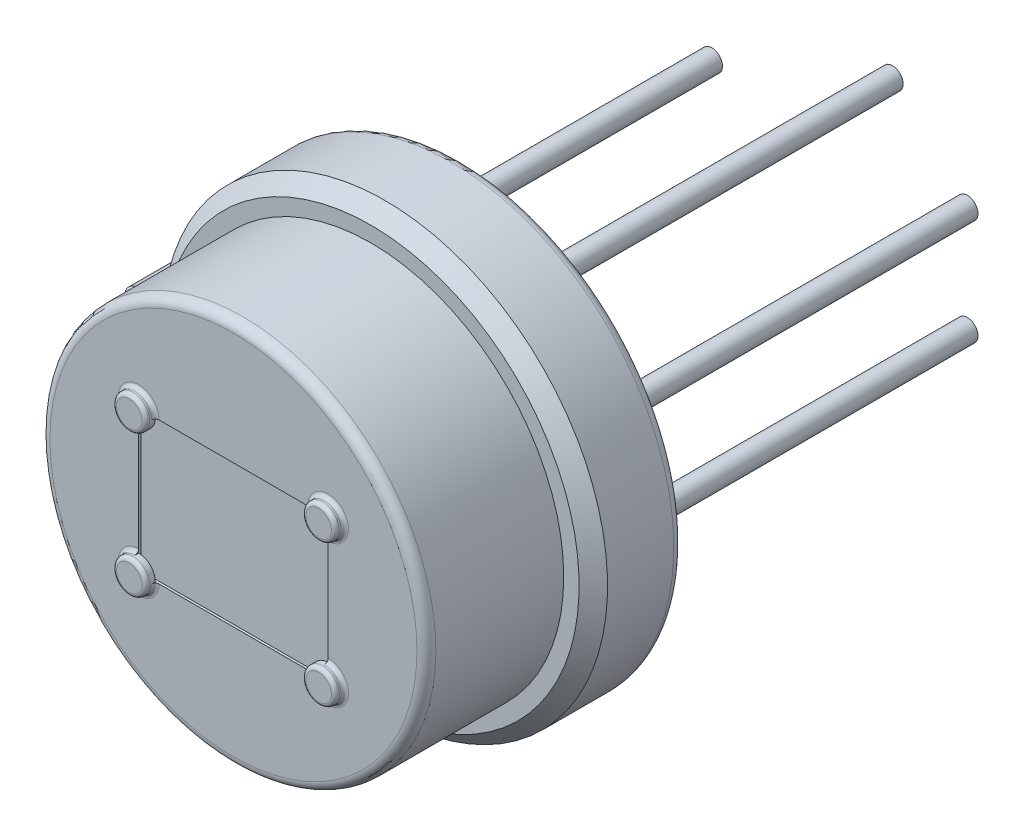
SolidWorks part; units mm, degrees
ref_plane "前视基准面" through (0, 0, 0) normal (0, 0, 1) x (1, 0, 0)
ref_plane "上视基准面" through (0, 0, 0) normal (0, 1, 0) x (1, 0, 0)
ref_plane "右视基准面" through (0, 0, 0) normal (1, 0, 0) x (0, 0, -1)
sketch "草图2" plane through (0, 0, 0) normal (0, 0, 1) x (1, 0, 0)
  line L0 (0, 6.1771) -> (0, -6.8536) construction
  line L1 (6.371, 0) -> (-6.6033, 0) construction
  line L2 (-5.5, 0.2) -> (-5.5, -0.2)
  line L3 (-5.2, -0.5) -> (-4.9356, -0.5)
  line L4 (-5.2, 0.5) -> (-4.9356, 0.5)
  arc A0 (-4.6394, -0.752) -> (-4.6394, 0.752) centre (0, 0) ccw
  arc A1 (-5.2, -0.5) -> (-5.5, -0.2) centre (-5.2, -0.2) cw
  arc A2 (-5.5, 0.2) -> (-5.2, 0.5) centre (-5.2, 0.2) cw
  arc A3 (-4.6394, -0.752) -> (-4.9356, -0.5) centre (-4.9356, -0.8) ccw
  arc A4 (-4.6394, 0.752) -> (-4.9356, 0.5) centre (-4.9356, 0.8) cw
  point P12 (-5.5, 0)
  point P14 (-5.5, -0.5)
  point P17 (-5.5, 0.5)
  point P19 (-4.6733, -0.5)
  point P22 (-4.6733, 0.5)
  dimension "D1" = 9.4
  dimension "D4" = 0.3
  dimension "D5" = 0.3
  dimension "D2" = 1
  dimension "D3" = 5.5
extrude "凸台-拉伸1" add sketch "草图2" along normal blind 1.9
sketch "草图3" plane through (0, 0, 1.9) normal (0, 0, 1) x (1, 0, 0)
  circle A0 centre (0, 0) radius 4.075
  dimension "D1" = 8.15
extrude "凸台-拉伸2" add sketch "草图3" along normal blind 2.9
sketch "草图4" plane through (0, 0, 0) normal (0, 0, -1) x (-1, 0, 0)
  line L0 (0, -4.9981) -> (0, 5.1357) construction
  line L1 (-5.2049, 0) -> (6.3427, 0) construction
  line L2 (0, 0) -> (-5.6057, -2.3219) construction
  line L3 (2.9056, -1.2035) -> (-5.7022, 2.3619) construction
  line L4 (1.1174, -2.6977) -> (-2.588, 6.248) construction
  circle A0 centre (0, 0) radius 2.92 construction
  circle A1 centre (-2.6977, -1.1174) radius 0.225
  circle A2 centre (-2.6977, 1.1174) radius 0.225
  circle A3 centre (-1.1174, 2.6977) radius 0.225
  circle A4 centre (2.6977, -1.1174) radius 0.225
  circle A5 centre (2.6977, 1.1174) radius 0.225
  circle A6 centre (1.1174, -2.6977) radius 0.225
  dimension "D1" = 5.84
  dimension "D3" = 0.45
  dimension "D6" = 0.45
  dimension "D7" = 0.45
  dimension "D8" = 0.45
  dimension "D2" = 22.5
  dimension "D4" = 45
  dimension "D5" = 45
extrude "凸台-拉伸3" add sketch "草图4" along normal blind 8
chamfer "倒角1" distance 0.3 angle 45 8 edges at (-5.5, 0, 1.9) (-5.4121, -0.4121, 1.9) (-5.4121, 0.4121, 1.9) (-5.0678, -0.5, 1.9) (-5.0678, 0.5, 1.9) (-4.7412, -0.5715, 1.9) (-4.7412, 0.5715, 1.9) (4.7, 0, 1.9)
fillet "圆角1" radius 0.2 9 edges at (-4.7412, -0.5715, 0) (-5.0678, -0.5, 0) (-5.4121, -0.4121, 0) (-5.5, 0, 0) (-5.4121, 0.4121, 0) (-5.0678, 0.5, 0) (-4.7412, 0.5715, 0) (4.075, 0, 4.8) (4.7, 0, 0)
sketch "草图6" plane through (0, 0, 4.8) normal (0, 0, 1) x (1, 0, 0)
  line L1 (-2, 1.5) -> (2, 1.5)
  line L2 (-2, 1.5) -> (-2, -1.5)
  line L3 (-2, -1.5) -> (2, -1.5)
  line L4 (2, 1.5) -> (2, -1.5)
  line L5 (-2, 1.5) -> (2, -1.5) construction
  line L6 (-2, -1.5) -> (2, 1.5) construction
  point P0 (0, 0)
  dimension "D1" = 4
  dimension "D2" = 3
extrude "切除-拉伸1" cut sketch "草图6" against normal blind 0.05
sketch "草图7" plane through (0, 0, 4.8) normal (0, 0, 1) x (1, 0, 0)
  circle A0 centre (-2, 1.5) radius 0.35
  circle A1 centre (2, 1.5) radius 0.35
  circle A2 centre (-2, -1.5) radius 0.35
  circle A3 centre (2, -1.5) radius 0.35
  dimension "D1" = 0.7
  dimension "D2" = 0.7
  dimension "D3" = 0.7
  dimension "D4" = 0.7
extrude "凸台-拉伸4" add sketch "草图7" along normal blind 0.2
fillet "圆角2" radius 0.08 8 edges at (-1.65, -1.5, 5) (2.35, -1.5, 5) (2.2475, -1.7475, 4.8) (-2.2475, -1.7475, 4.8) (2.2475, 1.7475, 4.8) (2.35, 1.5, 5) (-2.2475, 1.7475, 4.8) (-1.65, 1.5, 5)
